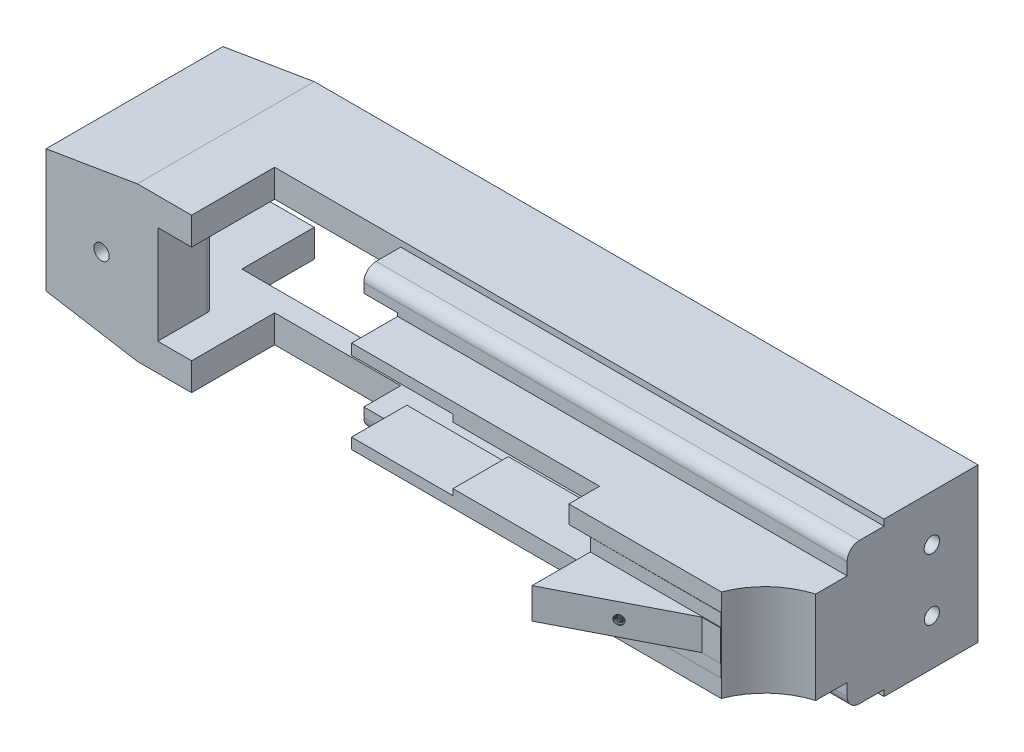
SolidWorks part; units mm, degrees
ref_plane "Front Plane" through (0, 0, 0) normal (0, 0, 1) x (1, 0, 0)
ref_plane "Top Plane" through (0, 0, 0) normal (0, 1, 0) x (1, 0, 0)
ref_plane "Right Plane" through (0, 0, 0) normal (1, 0, 0) x (0, 0, -1)
sketch "Sketch1" plane through (0, 0, 0) normal (0, 0, 1) x (1, 0, 0)
  line L0 (0, 0) -> (245.5, 0)
  line L1 (245.5, 0) -> (245.5, 50)
  line L2 (245.5, 50) -> (0, 50)
  line L3 (0, 50) -> (0, 0)
  dimension "D1" = 245.5
  dimension "D2" = 50
extrude "Boss-Extrude1" add sketch "Sketch1" along normal blind 57.55
sketch "Sketch2" plane through (0, 0, 0) normal (0, 0, -1) x (-1, 0, 0)
  line L0 (0, 9) -> (-205, 9)
  line L1 (0, 50) -> (0, 0) construction
  line L2 (-205, 9) -> (-205, 41)
  line L3 (-205, 41) -> (0, 41)
  line L4 (0, 41) -> (0, 9)
  line L5 (0, 0) -> (-245.5, 0) construction
  line L6 (-245.5, 50) -> (0, 50) construction
  dimension "D1" = 9
  dimension "D2" = 9
  dimension "D3" = 205
extrude "Cut-Extrude1" cut sketch "Sketch2" against normal blind 39.55
sketch "Sketch3" plane through (0, 0, 39.55) normal (0, 0, -1) x (-1, 0, 0)
  line L0 (-10, 9) -> (0, 9)
  line L1 (-205, 9) -> (0, 9) construction
  line L2 (0, 9) -> (0, 41)
  line L3 (0, 41) -> (-10, 41)
  line L4 (0, 41) -> (-205, 41) construction
  line L5 (-10, 41) -> (-10, 9)
  dimension "D1" = 10
extrude "Cut-Extrude2" cut sketch "Sketch3" against normal blind 5
sketch "Sketch4" plane through (0, 0, 39.55) normal (0, 0, -1) x (-1, 0, 0)
  line L0 (0, 9) -> (0, 41) construction
  line L1 (-205, 9) -> (-10, 9) construction
  circle A0 centre (-18.055, 25) radius 2.4875
  dimension "D1" = 4.975
  dimension "D2" = 18.055
  dimension "D3" = 16
extrude "Cut-Extrude3" cut sketch "Sketch4" against normal through all
sketch "Sketch5" plane through (0, 0, 0) normal (0, 0, -1) x (-1, 0, 0)
  line L1 (0, 50) -> (0, 41) construction
  line L4 (0, 45.028) -> (-29.689, 50)
  line L5 (-245.5, 50) -> (0, 50) construction
  line L7 (0, 45.028) -> (0, 51.6223)
  line L8 (0, 51.6223) -> (-29.689, 51.6223)
  line L9 (-29.689, 51.6223) -> (-29.689, 50)
extrude "Cut-Extrude4" cut sketch "Sketch5" against normal through all
sketch "Sketch6" plane through (0, 0, 0) normal (0, 0, -1) x (-1, 0, 0)
  line L1 (0, 9) -> (0, 0) construction
  line L4 (0, 4.972) -> (-29.689, 0)
  line L5 (0, 0) -> (-245.5, 0) construction
  line L7 (-29.689, 0) -> (0.6137, 0)
  line L8 (0.6137, 0) -> (0.6137, 4.972)
  line L9 (0.6137, 4.972) -> (0, 4.972)
extrude "Cut-Extrude5" cut sketch "Sketch6" against normal through all
sketch "Sketch7" plane through (0, 0, 0) normal (0, 0, -1) x (-1, 0, 0)
  line L0 (-29.689, 0) -> (-29.689, 9)
  line L1 (-29.689, 0) -> (-245.5, 0) construction
  line L2 (-205, 9) -> (0, 9) construction
  line L3 (0, 9) -> (0, 4.972) construction
  line L4 (-29.689, 9) -> (-112, 9)
  line L5 (-112, 9) -> (-112, 0)
  line L6 (-112, 0) -> (-29.689, 0)
  point P8 (-112, 4.5)
  dimension "D1" = 29.689
  dimension "D2" = 82.311
extrude "Cut-Extrude6" cut sketch "Sketch7" against normal blind 23.55
sketch "Sketch8" plane through (0, 0, 39.55) normal (0, 0, -1) x (-1, 0, 0)
  line L0 (-37.342, 9) -> (-37.342, 41)
  line L1 (-205, 9) -> (-10, 9) construction
  line L2 (-10, 41) -> (-205, 41) construction
  line L3 (0, 9) -> (0, 41) construction
  line L4 (-37.342, 9) -> (-99.342, 9)
  line L5 (-99.342, 9) -> (-99.342, 41)
  line L6 (-99.342, 41) -> (-37.342, 41)
  dimension "D1" = 37.342
  dimension "D2" = 62
extrude "Cut-Extrude7" cut sketch "Sketch8" against normal through all
sketch "Sketch9" plane through (0, 0, 39.55) normal (0, 0, -1) x (-1, 0, 0)
  line L0 (-99.342, 13.5) -> (-132.342, 13.5)
  line L1 (-99.342, 41) -> (-99.342, 9) construction
  line L2 (-132.342, 13.5) -> (-132.342, 36.5)
  line L3 (-132.342, 36.5) -> (-99.342, 36.5)
  line L4 (-99.342, 36.5) -> (-99.342, 13.5)
  line L5 (-205, 9) -> (-99.342, 9) construction
  line L6 (-99.342, 41) -> (-205, 41) construction
  dimension "D1" = 4.5
  dimension "D2" = 4.5
  dimension "D3" = 33
extrude "Cut-Extrude8" cut sketch "Sketch9" against normal through all
sketch "Sketch10" plane through (0, 0, 39.55) normal (0, 0, -1) x (-1, 0, 0)
  line L0 (-132.342, 34.196) -> (-184.342, 34.196)
  line L1 (-132.342, 36.5) -> (-132.342, 13.5) construction
  line L2 (-184.342, 34.196) -> (-184.342, 15.499)
  line L3 (-184.342, 15.499) -> (-132.342, 15.499)
  line L4 (-132.342, 15.499) -> (-132.342, 34.196)
  line L5 (-205, 9) -> (-99.342, 9) construction
  line L6 (-99.342, 41) -> (-205, 41) construction
  dimension "D1" = 6.499
  dimension "D2" = 6.804
  dimension "D3" = 52
extrude "Cut-Extrude9" cut sketch "Sketch10" against normal through all
sketch "Sketch11" plane through (0, 0, 39.55) normal (0, 0, -1) x (-1, 0, 0)
  line L0 (-184.342, 15.499) -> (-187.342, 15.499)
  line L1 (-187.342, 15.499) -> (-187.342, 34.2927)
  line L2 (-187.342, 34.2927) -> (-184.342, 34.196)
  line L3 (-184.342, 34.196) -> (-184.342, 15.499)
  dimension "D1" = 3
extrude "Cut-Extrude10" cut sketch "Sketch11" against normal blind 3
sketch "Sketch12" plane through (0, 50, 0) normal (0, 1, 0) x (1, 0, 0)
  line L0 (47.342, -57.55) -> (47.342, -30.55)
  line L1 (245.5, -57.55) -> (29.689, -57.55) construction
  line L2 (0, -57.55) -> (0, 0) construction
  line L3 (47.342, -30.55) -> (88.342, -30.55)
  line L4 (88.342, -30.55) -> (88.342, -57.55)
  line L5 (88.342, -57.55) -> (47.342, -57.55)
  point P7 (88.342, -44.05)
  dimension "D1" = 47.342
  dimension "D2" = 41
  dimension "D3" = 27
extrude "Cut-Extrude11" cut sketch "Sketch12" against normal through all
sketch "Sketch13" plane through (0, 50, 0) normal (0, 1, 0) x (1, 0, 0)
  line L0 (88.342, -57.55) -> (88.342, -42.55)
  line L1 (88.342, -57.55) -> (88.342, -30.55) construction
  line L2 (88.342, -42.55) -> (99.342, -42.55)
  line L3 (99.342, -42.55) -> (99.342, -57.55)
  line L4 (245.5, -57.55) -> (88.342, -57.55) construction
  line L5 (99.342, -57.55) -> (88.342, -57.55)
  dimension "D1" = 15
  dimension "D2" = 11
extrude "Cut-Extrude12" cut sketch "Sketch13" against normal through all
sketch "Sketch14" plane through (0, 50, 0) normal (0, 1, 0) x (1, 0, 0)
  line L0 (99.342, -57.55) -> (99.342, -42.55)
  line L1 (99.342, -42.55) -> (245.5, -42.55)
  line L2 (245.5, -57.55) -> (245.5, 0) construction
  line L3 (245.5, -42.55) -> (245.5, -57.55)
  line L4 (245.5, -57.55) -> (99.342, -57.55)
extrude "Cut-Extrude13" cut sketch "Sketch14" against normal blind 10
sketch "Sketch15" plane through (0, 40, 0) normal (0, 1, 0) x (1, 0, 0)
  line L0 (180, -57.55) -> (180, -86.52)
  line L1 (99.342, -57.55) -> (245.5, -57.55) construction
  line L2 (180, -86.52) -> (245.5, -86.52)
  line L3 (245.5, -86.52) -> (245.5, -57.55)
  line L4 (245.5, -57.55) -> (180, -57.55)
  line L5 (0, -57.55) -> (0, 0) construction
  dimension "D1" = 28.97
  dimension "D2" = 180
extrude "Boss-Extrude2" add sketch "Sketch15" against normal blind 30
sketch "Sketch17" plane through (0, 40, 0) normal (0, 1, 0) x (1, 0, 0)
  line L0 (180, -67.55) -> (187, -67.55)
  line L1 (180, -57.55) -> (180, -86.52) construction
  line L2 (99.342, -57.55) -> (180, -57.55) construction
  line L3 (187, -67.55) -> (187, -86.52)
  line L4 (180, -86.52) -> (245.5, -86.52) construction
  line L5 (187, -86.52) -> (180, -86.52)
  line L6 (180, -86.52) -> (180, -67.55)
  dimension "D1" = 10
  dimension "D2" = 7
extrude "Cut-Extrude14" cut sketch "Sketch17" against normal through all
sketch "Sketch18" plane through (0, 0, 57.55) normal (0, 0, -1) x (-1, 0, 0)
  line L0 (-180, 15.499) -> (-184.342, 15.499)
  line L1 (-184.342, 15.499) -> (-184.342, 34.196)
  line L2 (-184.342, 34.196) -> (-180, 34.196)
  line L3 (-180, 34.196) -> (-180, 15.499)
extrude "Cut-Extrude15" cut sketch "Sketch18" against normal through all
sketch "Sketch20" plane through (0, 0, 67.55) normal (0, 0, 1) x (1, 0, 0)
  line L0 (184.342, 34.196) -> (187, 34.196)
  line L1 (187, 10) -> (187, 40) construction
  line L2 (184.342, 34.196) -> (184.342, 15.499)
  line L3 (184.342, 15.499) -> (187, 15.499)
  line L4 (187, 15.499) -> (187, 34.196)
extrude "Cut-Extrude16" cut sketch "Sketch20" against normal blind 18
sketch "Sketch21" plane through (0, 40, 0) normal (0, 1, 0) x (1, 0, 0)
  line L1 (245.5, -86.52) -> (245.5, -42.55) construction
  line L2 (245.5, -67.597) -> (245.5, -86.52)
  line L3 (245.5, -86.52) -> (187, -86.52)
  line L5 (245.5, -67.597) -> (187, -67.55)
  line L7 (187, -67.55) -> (176.1532, -67.55)
  line L8 (176.1532, -67.55) -> (176.1532, -86.52)
  line L9 (176.1532, -86.52) -> (187, -86.52)
  dimension "D1" = 18.923
extrude "Cut-Extrude17" cut sketch "Sketch21" against normal blind 10
sketch "Sketch27" plane through (0, 40, 0) normal (0, 1, 0) x (1, 0, 0)
  line L1 (180, -57.55) -> (180, -67.55) construction
  line L2 (180, -67.519) -> (245.5, -67.519)
  line L3 (245.5, -67.597) -> (245.5, -42.55) construction
  line L4 (187, -67.55) -> (180, -67.55) construction
  line L5 (180, -67.519) -> (180, -67.55)
  line L6 (180, -67.55) -> (245.5, -67.597)
  line L7 (245.5, -67.597) -> (245.5, -67.519)
  dimension "D1" = 0.031
extrude "Cut-Extrude21" cut sketch "Sketch27" against normal blind 5.804
sketch "Sketch22" plane through (0, 10, 0) normal (0, -1, 0) x (1, 0, 0)
  line L0 (187, 67.55) -> (245.5, 67.55)
  line L1 (245.5, 86.52) -> (245.5, 57.55) construction
  line L2 (245.5, 67.55) -> (245.5, 86.52)
  line L3 (245.5, 86.52) -> (187, 86.52)
  line L4 (187, 86.52) -> (187, 67.55)
extrude "Cut-Extrude18" cut sketch "Sketch22" against normal blind 10
sketch "Sketch23" plane through (0, 30, 0) normal (0, 1, 0) x (1, 0, 0)
  line L9 (187, -67.55) -> (187, -86.52) construction
  line L12 (223.471, -67.772) -> (187, -86.52)
  line L13 (223.471, -67.772) -> (245.5, -67.772)
  line L14 (187, -86.52) -> (245.5, -86.52)
  line L15 (245.5, -86.52) -> (245.5, -67.772)
  dimension "D2" = 36.471
extrude "Cut-Extrude20" cut sketch "Sketch23" against normal through all
sketch "Sketch29" plane through (74.2658, 0, 144.4713) normal (0.4572, 0, 0.8894) x (0.8894, 0, -0.4572)
  line L0 (126.7571, 20) -> (126.7571, 30) construction
  line L1 (167.7646, 30) -> (126.7571, 30) construction
  circle A0 centre (147.7571, 24.882) radius 1.5
  dimension "D3" = 3
  dimension "D1" = 21
  dimension "D2" = 5.118
extrude "Cut-Extrude22" cut sketch "Sketch29" against normal blind 8.5
sketch "Sketch31" plane through (0, 0, 0) normal (0, -1, 0) x (1, 0, 0)
  line L0 (88.342, 30.55) -> (245.5, 30.55)
  line L2 (245.5, 57.55) -> (245.5, 0) construction
  line L3 (245.5, 30.55) -> (245.5, 57.55)
  line L4 (245.5, 57.55) -> (99.342, 57.55)
  line L5 (99.342, 57.55) -> (88.342, 57.55)
  line L6 (88.342, 57.55) -> (88.342, 30.55)
extrude "Cut-Extrude23" cut sketch "Sketch31" against normal blind 2
sketch "Sketch32" plane through (0, 2, 0) normal (0, -1, 0) x (1, 0, 0)
  line L0 (99.342, 42.55) -> (245.5, 42.55)
  line L1 (245.5, 30.55) -> (245.5, 57.55) construction
  line L2 (245.5, 42.55) -> (245.5, 57.55)
  line L3 (245.5, 57.55) -> (99.342, 57.55)
  line L4 (99.342, 57.55) -> (99.342, 42.55)
extrude "Cut-Extrude24" cut sketch "Sketch32" against normal blind 8
fillet "Fillet2" radius 4 1 edges at (166.921, 2, 42.55)
sketch "Sketch35" plane through (0, 0, 67.55) normal (0, 0, 1) x (1, 0, 0)
  line L0 (245.5, 20) -> (245.5, 15.797)
  line L1 (245.5, 15.797) -> (187, 15.797)
  line L2 (187, 20) -> (187, 15.499) construction
  line L3 (187, 15.797) -> (187, 20)
  line L4 (187, 20) -> (245.5, 20)
extrude "Boss-Extrude4" add sketch "Sketch35" along normal blind 0.08
sketch "Sketch37" plane through (0, 50, 0) normal (0, 1, 0) x (1, 0, 0)
  line L0 (88.342, -30.55) -> (245.5, -30.55)
  line L1 (245.5, -42.55) -> (245.5, 0) construction
  line L2 (245.5, -30.55) -> (245.5, -42.55)
  line L3 (245.5, -42.55) -> (88.342, -42.55) construction
  line L4 (245.5, -42.55) -> (88.342, -42.55)
  line L5 (88.342, -42.55) -> (88.342, -30.55)
extrude "Cut-Extrude25" cut sketch "Sketch37" against normal blind 2
fillet "Fillet3" radius 4 1 edges at (166.921, 48, 42.55)
sketch "Sketch38" plane through (205, 0, 0) normal (-1, 0, 0) x (0, 0, 1)
  line L0 (30.55, 0) -> (0, 0) construction
  line L1 (30.55, 50) -> (0, 50) construction
  line L2 (0, 41) -> (0, 9) construction
  circle A0 centre (15, 15) radius 2.4445
  circle A1 centre (15, 35) radius 2.5019
  dimension "D1" = 15
  dimension "D2" = 15
  dimension "D3" = 15
  dimension "D4" = 15
extrude "Cut-Extrude26" cut sketch "Sketch38" against normal through all
sketch "Sketch39" plane through (0, 0, 67.772) normal (0, 0, 1) x (1, 0, 0)
  line L0 (229.571, 20) -> (229.571, 30)
  line L1 (223.471, 20) -> (245.5, 20) construction
  line L2 (245.5, 30) -> (223.471, 30) construction
  line L3 (223.471, 20) -> (223.471, 30) construction
  line L4 (229.571, 20) -> (229.571, 12.2217)
  line L6 (253.2973, 12.2217) -> (254.0062, 41.842)
  line L7 (254.0062, 41.842) -> (229.571, 41.842)
  line L8 (229.571, 41.842) -> (229.571, 30)
  line L9 (229.571, 12.2217) -> (229.571, 4.0695)
  line L10 (229.571, 4.0695) -> (253.2973, 4.0695)
  line L11 (253.2973, 4.0695) -> (253.2973, 12.2217)
  dimension "D1" = 6.1
extrude "Cut-Extrude27" cut sketch "Sketch39" against normal blind 15
sketch "Sketch42" plane through (0, 10, 0) normal (0, -1, 0) x (1, 0, 0)
  line L0 (229.571, 67.55) -> (229.571, 52.772)
  line L1 (229.571, 52.772) -> (245.5, 52.772)
  arc A0 (245.5, 52.772) -> (229.571, 67.55) centre (252.4707, 76.2594) cw
  dimension "D1" = 24.5
extrude "Boss-Extrude5" add sketch "Sketch42" against normal blind 30
thread "Thread1" pitch 0.5 method extrude profile "Thread Profile2" start angle 0, offset 0, length 6.5, pitch 0.5, diameter 3
ref_plane "Plane2" through (204.3428, 24.882, 77.6049) normal (0, -1, 0) x (-0.8894, 0, 0.4572)
sketch "Thread Profile2" plane through (204.3428, 24.882, 77.6049) normal (0, -1, 0) x (-0.8894, 0, 0.4572)
  line L0 (0, 0) -> (0, 0.5) construction
  line L11 (0, 0) -> (0, 0.4375)
  line L12 (0, 0.4375) -> (-0.2706, 0.2812)
  line L13 (-0.2706, 0.2812) -> (-0.2706, 0.1562)
  line L15 (-0.2706, 0.1562) -> (0, 0)
  line L17 (-0.2706, 0.2187) -> (0, 0.2187) construction
  point P2 (0, 0)
  dimension "Pitch" = 0.5
  dimension "Profile_Angle" = 60
  dimension "Profile_Land" = 0.125
  dimension "Profile_Height" = 0.2706
fillet "Fillet4" radius 4 1 edges at (10, 25, 39.55)
sketch "Sketch43" plane through (0, 0, 57.55) normal (0, 0, 1) x (1, 0, 0)
  line L0 (37.342, 9) -> (36.342, 9)
  line L1 (37.342, 9) -> (37.342, 41)
  line L2 (37.342, 41) -> (36.342, 41)
  line L3 (36.342, 41) -> (36.342, 9)
  dimension "D1" = 1
extrude "Cut-Extrude28" cut sketch "Sketch43" against normal through all
fillet "Fillet7" radius 2 1 edges at (36.342, 25, 39.55)
